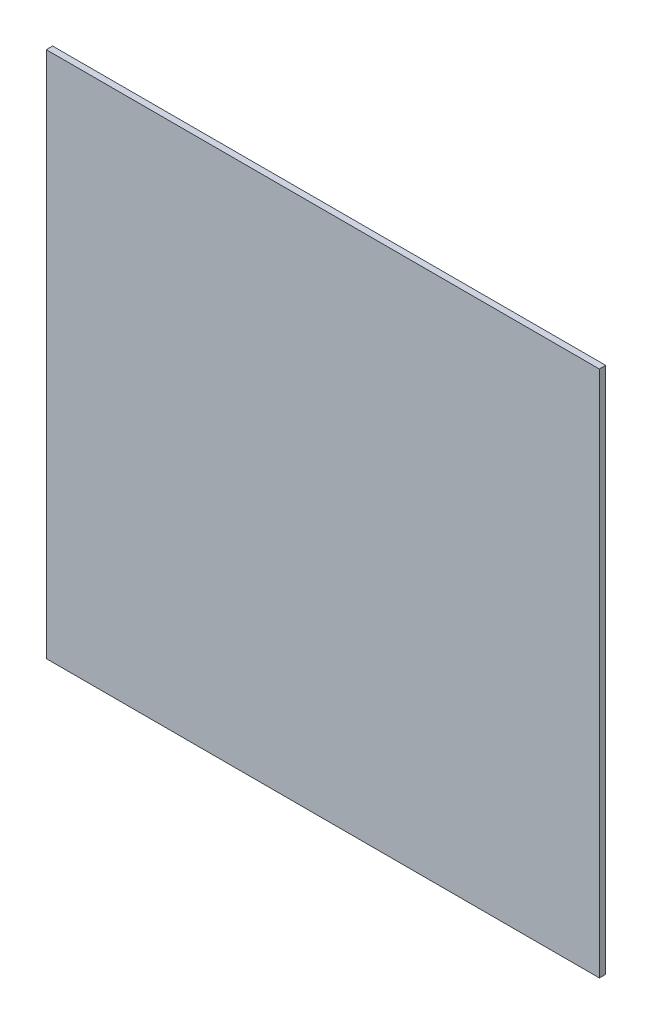
SolidWorks part; units mm, degrees
ref_plane "Спереди" through (0, 0, 0) normal (0, 0, 1) x (1, 0, 0)
ref_plane "Сверху" through (0, 0, 0) normal (0, 1, 0) x (1, 0, 0)
ref_plane "Справа" through (0, 0, 0) normal (1, 0, 0) x (0, 0, -1)
other "Configuration Table"
sketch "Эскиз1" plane through (0, 0, 0) normal (0, 0, 1) x (1, 0, 0)
  line L0 (0, -493.6) -> (-524, -493.6) construction
  line L1 (0, -493.6) -> (-524, -493.6)
  line L2 (0, -493.6) -> (0, 6)
  line L3 (0, 6) -> (-524, 6)
  line L4 (-524, -493.6) -> (-524, 6)
  line L5 (0, 6) -> (-518, 6) construction
  line L6 (0, 6) -> (0, -493.6) construction
  line L7 (-524, -865.6) -> (-524, 6) construction
extrude "Бобышка-Вытянуть1" add sketch "Эскиз1" against normal blind 6
equation "\"Толщина стенки\" = 6"
equation "\"Ширина груза\"= 420"
equation "\"Глубина груза\"= 490"
equation "\"Высота груза\"= 297"
equation "\"Ширина ячейки\"= \"Ширина груза\" + 10"
equation "\"Глубина ячейки\"= \"Глубина груза\" + 10"
equation "\"Высота ячейки\"= \"Высота груза\" + 10 + 13"
equation "\"Колво ячеек ширина\"= 2"
equation "\"Колво ячеек высота\"= 2"
equation "\"Крепление дверцы\"= 5 "
equation "\"Ширина рейки\"= \"Толщина шестерни\""
equation "\"Высота рейки\"= 20"
equation "\"Высота пола\"= \"Толщина стенки\" * 2"
equation "\"Колво полозьев\"= 5"
equation "\"Отступ рейки\"= 20"
equation "\"Глубина каретки\"= \"Глубина ячейки\" + 30 + \"Мотор Y высота корпуса\" + 20"
equation "\"Длинна рейки\"= ( \"Ширина ячейки\" + \"Толщина стенки\" + \"Крепление дверцы\" ) * \"Колво ячеек ширина\" + \"Ширина ячейки выгрузки\" * \"Колво выгрузки\" + \"Толщина стенки\""
equation "\"Отступ шпильки\"= 26"
equation "\"Диаметр шпильки\"= 5"
equation "\"Длинна шпильки\"= ( \"Высота ячейки\" + \"Толщина стенки\" + \"Высота пола\" ) * \"Колво ячеек высота\" + ( \"Толщина стенки\" + \"Отступ рейки\" ) * 2 "
equation "\"Ширина пластины\"= 50  "
equation "\"Высота зона выгрузки\"= \"Высота ячейки\" * 2 + \"Толщина стенки\" * 2"
equation "\"Колво выгрузки\"= 1"
equation "\"Ширина ячейки выгрузки\"= \"Ширина ячейки\" + \"Толщина стенки\" + \"Отступ крепления мотора фиксации\"*2"
equation "\"Отступ крепления мотора фиксации\" = 30"
equation "\"Мотор X ширина корпуса\"= 42.3"
equation "\"Мотор X высота корпуса\"= 42.3"
equation "\"Мотор X длина корпуса\"= 40"
equation "\"Мотор X вылет вала\"= 19.8"
equation "\"Мотор Y ширина корпуса\"= 42.3"
equation "\"Мотор Y высота корпуса\"= 42.3"
equation "\"Мотор Y длина корпуса\"= 48"
equation "\"Мотор Y вылет вала\"= 30"
equation "\"Мотор Z ширина корпуса\"= 42"
equation "\"Мотор Z высота корпуса\"= 42"
equation "\"Мотор Z длина корпуса\"= 40"
equation "\"Мотор Z вылет вала\"= 23"
equation "\"Мотор диаметр вала ПРЕДВ\"= 5"
equation "\"Мотор шаг крепления ПРЕДВ\"= 31"
equation "\"Мотор диаметр отверстий ПРЕДВ\"= 3"
equation "\"Мотор глубина отверстий ПРЕДВ\"= 4.5"
equation "\"Мотор диаметр буртика ПРЕДВ\"= 22"
equation "\"Мотор высота буртика ПРЕДВ\"= 2"
equation "\"Мотор диаметр шкива ПРЕДВ\"= 16"
equation "\"Мотор длина шкива ПРЕДВ\"= 12"
equation "\"Мотор отступ шкива ПРЕДВ\"= 5"
equation "\"Мотор X шаг градусов\"= 1.8"
equation "\"Мотор Y шаг градусов\"= 1.8"
equation "\"Мотор Z шаг градусов\"= 1.8"
equation "\"Мотор Y диаметр ротора\"= 25.78"
equation "\"Толщина шестерни\"= 10"
equation "\"D1@Бобышка-Вытянуть1\"=\"Толщина стенки\""
